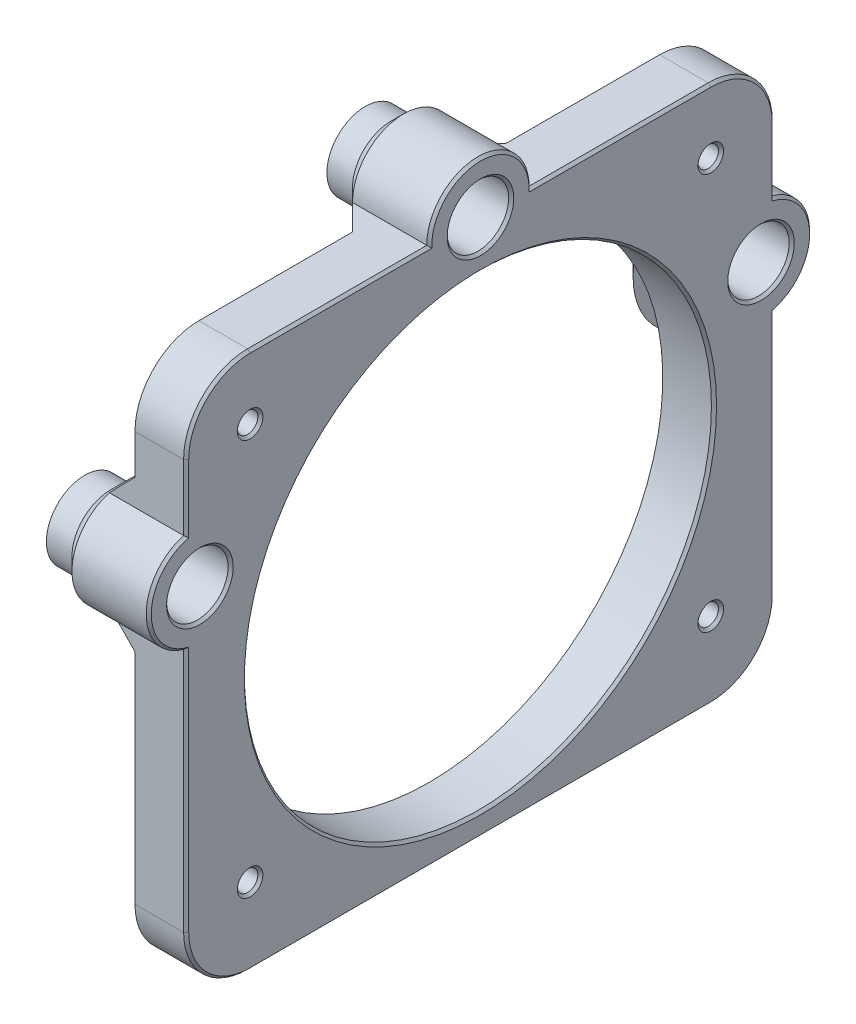
SolidWorks part; units mm, degrees
ref_plane "前视基准面" through (0, 0, 0) normal (0, 0, 1) x (1, 0, 0)
ref_plane "上视基准面" through (0, 0, 0) normal (0, 1, 0) x (1, 0, 0)
ref_plane "右视基准面" through (0, 0, 0) normal (1, 0, 0) x (0, 0, -1)
other "Configuration Table"
sketch "草图1" plane through (0, 0, 0) normal (1, 0, 0) x (0, 0, -1)
  line L1 (0, 0) -> (46, 0)
  line L2 (0, 0) -> (0, -41)
  line L3 (0, -41) -> (46, -41)
  line L4 (46, 0) -> (46, -41)
  circle A0 centre (5, -5) radius 0.8
  circle A1 centre (41, -5) radius 0.8
  circle A2 centre (5, -36) radius 0.8
  circle A3 centre (41, -36) radius 0.8
  dimension "D1" = 1.6
  dimension "D2" = 1.6
  dimension "D3" = 1.6
  dimension "D4" = 1.6
  dimension "D7" = 46
  dimension "D8" = 41
  dimension "D5" = 5
  dimension "D6" = 5
  dimension "D9" = 5
  dimension "D10" = 5
  dimension "D11" = 5
  dimension "D12" = 5
  dimension "D13" = 5
  dimension "D14" = 5
extrude "凸台-拉伸1" add sketch "草图1" along normal blind 4
sketch "草图2" plane through (0, 0, 0) normal (-1, 0, 0) x (0, 0, 1)
  line L1 (-46, 0) -> (0, 0) construction
  circle A0 centre (-44.925, -14) radius 4
  circle A1 centre (-1.075, -14) radius 4
  circle A2 centre (-23, 0) radius 4
  point P8 (-23, 0)
  dimension "D7" = 8
  dimension "D8" = 8
  dimension "D9" = 8
  dimension "D2" = 0
  dimension "D3" = 14
  dimension "D4" = 14
  dimension "D5" = 43.85
  dimension "D6" = 21.925
extrude "凸台-拉伸2" add sketch "草图2" against normal blind 4
sketch "草图3" plane through (0, 0, 0) normal (-1, 0, 0) x (0, 0, 1)
  circle A0 centre (-44.925, -14) radius 3
  circle A1 centre (-23, 0) radius 3
  circle A2 centre (-1.075, -14) radius 3
  dimension "D1" = 6
  dimension "D2" = 6
  dimension "D3" = 6
extrude "凸台-拉伸3" add sketch "草图3" along normal blind 5
sketch "草图4" plane through (-5, 0, 0) normal (-1, 0, 0) x (0, 0, 1)
  circle A0 centre (-44.925, -14) radius 1.6
  circle A1 centre (-23, 0) radius 1.6
  circle A2 centre (-1.075, -14) radius 1.6
  dimension "D1" = 3.2
  dimension "D2" = 3.2
  dimension "D3" = 3.2
extrude "切除-拉伸2" cut sketch "草图4" against normal through all
sketch "草图5" plane through (4, 0, 0) normal (1, 0, 0) x (0, 0, -1)
  circle A0 centre (1.075, -14) radius 2.4
  circle A1 centre (23, 0) radius 2.4
  circle A2 centre (44.925, -14) radius 2.4
  dimension "D1" = 4.8
  dimension "D2" = 4.8
  dimension "D3" = 4.8
extrude "切除-拉伸3" cut sketch "草图5" against normal blind 4.2
chamfer "倒角2" distance 3 angle 45 3 edges at (0, -14, -4.075) (0, 0, -26) (0, -14, -47.925)
sketch "草图6" plane through (0, 0, 0) normal (-1, 0, 0) x (0, 0, 1)
  circle A0 centre (-23, -22) radius 18.25
  dimension "D1" = 36.5
extrude "切除-拉伸4" cut sketch "草图6" against normal blind 4
sketch "草图7" plane through (0, -41, 0) normal (0, -1, 0) x (-1, 0, 0)
  line L1 (0, 0) -> (-4, 0)
  line L2 (0, 0) -> (0, 46)
  line L3 (0, 46) -> (-4, 46)
  line L4 (-4, 0) -> (-4, 46)
extrude "凸台-拉伸4" add sketch "草图7" along normal blind 1
fillet "圆角2" radius 5 4 edges at (2, 0, 0) (2, 0, -46) (2, -42, -46) (2, -42, 0)
chamfer "倒角3" distance 0.2 angle 45 22 edges at (4, -36, -41.8) (4, -5, -41.8) (4, -5, -5.8) (4, -36, -5.8) (4, 4, -23) (4, 0, -34) (4, -1.4645, -44.5355) (4, -7.5736, -46) (4, -14, -48.925) (4, -27.4264, -46) (4, -40.5355, -44.5355) (4, -42, -23) (4, -40.5355, -1.4645) (4, -27.4264, 0) (4, -14, 2.925) (4, -7.5736, 0) (4, -1.4645, -1.4645) (4, 0, -12) (4, -14, -47.325) (4, 0, -25.4) (4, -14, -3.475) (4, -22, -4.75)
equation "\"D7@草图1\"=36+10"
equation "\"D8@草图1\"=31+10"
equation "\"D6@草图2\"=\"D5@草图2\"/2"
